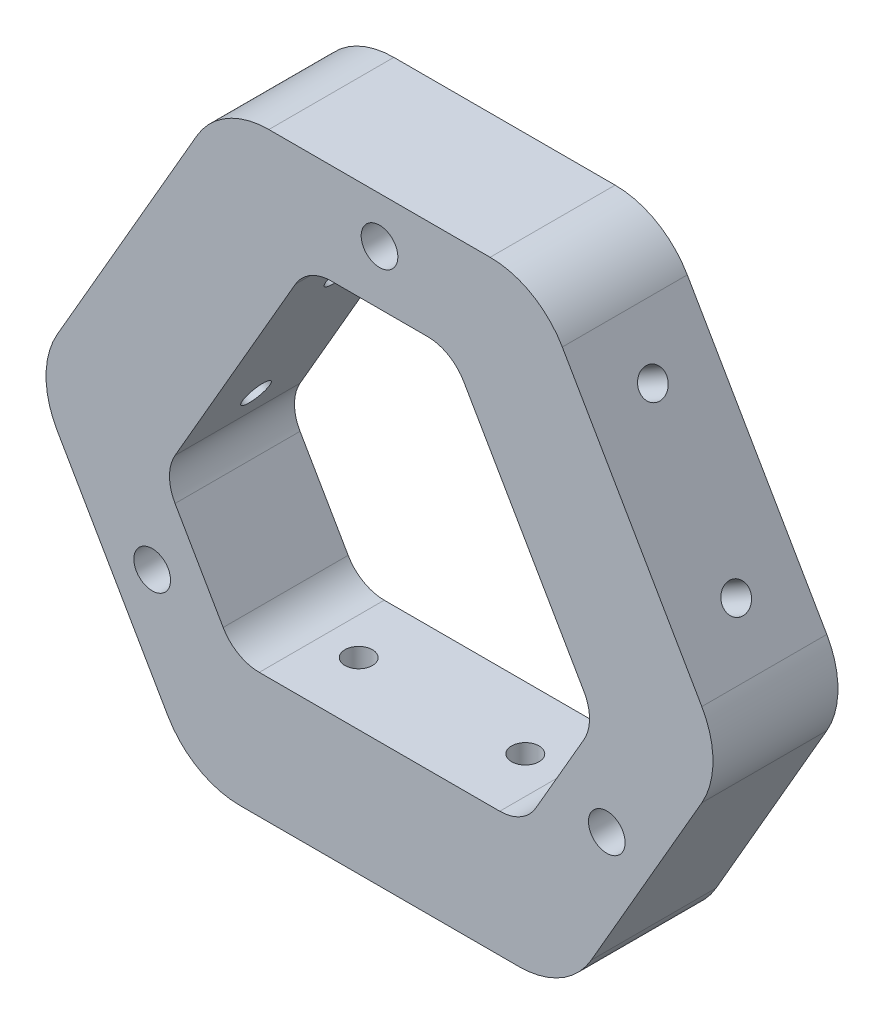
SolidWorks part; units mm, degrees
material "PLA"
ref_plane "前视基准面" through (0, 0, 0) normal (0, 0, 1) x (1, 0, 0)
ref_plane "上视基准面" through (0, 0, 0) normal (0, 1, 0) x (1, 0, 0)
ref_plane "右视基准面" through (0, 0, 0) normal (1, 0, 0) x (0, 0, -1)
other "Configuration Table"
sketch "草图1" plane through (0, 0, 0) normal (0, 0, 1) x (1, 0, 0)
  line L0 (0, 70) -> (-60.6218, -35)
  line L5 (-60.6218, -35) -> (60.6218, -35)
  line L6 (60.6218, -35) -> (0, 70)
  line L11 (0, 70) -> (0, 0) construction
  line L12 (0, 0) -> (30.3109, 17.5) construction
  line L13 (0, 0) -> (0, -35) construction
  line L14 (0, 40) -> (-34.641, -20)
  line L15 (-34.641, -20) -> (34.641, -20)
  line L16 (34.641, -20) -> (0, 40)
  line L17 (34.641, -20) -> (47.6314, -12.5) construction
  line L18 (34.641, -20) -> (34.641, -35) construction
  dimension "D1" = 15
  dimension "D2" = 35
extrude "凸台-拉伸1" add sketch "草图1" along normal blind 15
fillet "圆角1" radius 10 3 edges at (-60.6218, -35, 7.5) (60.6218, -35, 7.5) (0, 70, 7.5)
fillet "圆角2" radius 5 3 edges at (34.641, -20, 7.5) (-34.641, -20, 7.5) (0, 40, 7.5)
sketch "草图2" plane through (0, -35, 0) normal (0, -1, 0) x (1, 0, 0)
  line L0 (0, 0) -> (0, 36.777) construction
  line L1 (-43.3013, 0) -> (43.3013, 0) construction
  line L2 (-43.3013, 7.5) -> (66.3455, 7.5) construction
  line L3 (-43.3013, 15) -> (-43.3013, 0) construction
  circle A0 centre (-10, 7.5) radius 1.65
  circle A1 centre (10, 7.5) radius 1.65
  dimension "D1" = 20
  dimension "D2" = 3.3
extrude "切除-拉伸1" cut sketch "草图2" against normal blind 20
sketch "草图4" plane through (30.3109, 17.5, 0) normal (0.866, 0.5, 0) x (0, 0, -1)
  line L0 (0, 0) -> (-57.8219, 0) construction
  line L1 (0, 43.3013) -> (-15, 43.3013) construction
  circle A0 centre (-7.5, 10) radius 1.65
  circle A1 centre (-7.5, -10) radius 1.65
  point P9 (-7.5, 43.3013)
  dimension "D1" = 20
  dimension "D2" = 3.3
extrude "切除-拉伸2" cut sketch "草图4" against normal blind 20
sketch "草图5" plane through (-30.3109, 17.5, 0) normal (-0.866, 0.5, 0) x (0, 0, 1)
  line L0 (0, 0) -> (38.3926, 0) construction
  line L1 (15, 43.3013) -> (0, 43.3013) construction
  circle A0 centre (7.5, 10) radius 1.65
  circle A1 centre (7.5, -10) radius 1.65
  point P9 (7.5, 43.3013)
  dimension "D1" = 20
  dimension "D2" = 3.3
extrude "切除-拉伸3" cut sketch "草图5" against normal blind 20
sketch "草图6" plane through (0, 0, 15) normal (0, 0, 1) x (1, 0, 0)
  line L0 (-17.3205, 40) -> (17.3205, 40)
  line L1 (-8.6603, 55) -> (-51.9615, -20) construction
  line L2 (51.9615, -20) -> (8.6603, 55) construction
  line L3 (43.3013, -5) -> (25.9808, -35)
  line L4 (-25.9808, -35) -> (-43.3013, -5)
  point P13 (0, 0)
  line M3 (-8.6603, 55) -> (-51.9615, -20)
  arc M4 (-51.9615, -20) -> (-43.3013, -35) centre (-43.3013, -25) ccw
  line M5 (-43.3013, -35) -> (43.3013, -35)
  arc M6 (43.3013, -35) -> (51.9615, -20) centre (43.3013, -25) ccw
  line M7 (51.9615, -20) -> (8.6603, 55)
  arc M8 (8.6603, 55) -> (-8.6603, 55) centre (0, 50) ccw
  dimension "D1" = 40
  dimension "D2" = 3
extrude "切除-拉伸4" cut sketch "草图6" against normal blind 15 contours L0 M3 M7 M8 | L4 M5 M3 M4 | L3 M7 M5 M6 region at (0, 48.0803, 15) region at (-41.6388, -24.0402, 15) region at (41.6388, -24.0402, 15)
sketch "草图7" plane through (0, 0, 15) normal (0, 0, 1) x (1, 0, 0)
  line L0 (-8.6603, 25) -> (8.6603, 25)
  line L1 (-4.3301, 32.5) -> (-30.3109, -12.5) construction
  line L2 (30.3109, -12.5) -> (4.3301, 32.5) construction
  line L3 (25.9808, -5) -> (17.3205, -20)
  line L4 (-17.3205, -20) -> (-25.9808, -5)
  point P13 (0, 0)
  line M9 (-30.3109, -12.5) -> (-4.3301, 32.5)
  arc M10 (-4.3301, 32.5) -> (4.3301, 32.5) centre (0, 30) cw
  line M11 (4.3301, 32.5) -> (30.3109, -12.5)
  arc M12 (30.3109, -12.5) -> (25.9808, -20) centre (25.9808, -15) cw
  line M13 (25.9808, -20) -> (-25.9808, -20)
  arc M14 (-25.9808, -20) -> (-30.3109, -12.5) centre (-25.9808, -15) cw
  dimension "D1" = 25
  dimension "D2" = 3
extrude "凸台-拉伸2" add sketch "草图7" against normal up to surface (15 mm away) contours L0 M9 M11 M10 | L4 M13 M9 M14 | L3 M11 M13 M12 region at (0, 29.0402, 15) region at (-25.1495, -14.5201, 15) region at (25.1495, -14.5201, 15) up to face at (0, 0, 0)
sketch "草图8" plane through (0, 0, 15) normal (0, 0, 1) x (1, 0, 0)
  line L0 (-19.0526, 37) -> (19.0526, 37)
  line L1 (-17.3205, 40) -> (-43.3013, -5) construction
  line L2 (43.3013, -5) -> (17.3205, 40) construction
  line L3 (-17.3205, 40) -> (17.3205, 40) construction
  line L4 (41.5692, -2) -> (22.5167, -35)
  line L5 (-22.5167, -35) -> (-41.5692, -2)
  point P14 (0, 0)
  line M9 (17.3205, 40) -> (-17.3205, 40)
  line M10 (-17.3205, 40) -> (-43.3013, -5)
  line M11 (-43.3013, -5) -> (-25.9808, -35)
  line M12 (-25.9808, -35) -> (25.9808, -35)
  line M13 (25.9808, -35) -> (43.3013, -5)
  line M14 (43.3013, -5) -> (17.3205, 40)
  dimension "D1" = 3
  dimension "D2" = 3
extrude "切除-拉伸5" cut sketch "草图8" against normal through all contours L0 M10 M14 M9 | L5 M12 M10 M11 | L4 M14 M12 M13 region at (0, 38.4762, 15) region at (-33.3214, -19.2381, 15) region at (33.3214, -19.2381, 15)
fillet "圆角3" radius 10 6 edges at (19.0526, 37, 7.5) (41.5692, -2, 7.5) (22.5167, -35, 7.5) (-22.5167, -35, 7.5) (-41.5692, -2, 7.5) (-19.0526, 37, 7.5)
fillet "圆角4" radius 5 6 edges at (-25.9808, -5, 7.5) (-17.3205, -20, 7.5) (17.3205, -20, 7.5) (25.9808, -5, 7.5) (8.6603, 25, 7.5) (-8.6603, 25, 7.5)
sketch "草图9" plane through (0, 0, 15) normal (0, 0, 1) x (1, 0, 0)
  line L0 (0, 0) -> (0, 37) construction
  line L1 (-13.2791, 37) -> (13.2791, 37) construction
  circle A0 centre (0, 0) radius 31.5 construction
  circle A1 centre (0, 31.5) radius 2.2
  circle A2 centre (27.2798, -15.75) radius 2.2
  circle A3 centre (-27.2798, -15.75) radius 2.2
  point P14 (0, 0)
  dimension "D1" = 63
  dimension "D2" = 4.4
  dimension "D3" = 3
extrude "切除-拉伸6" cut sketch "草图9" against normal through all
